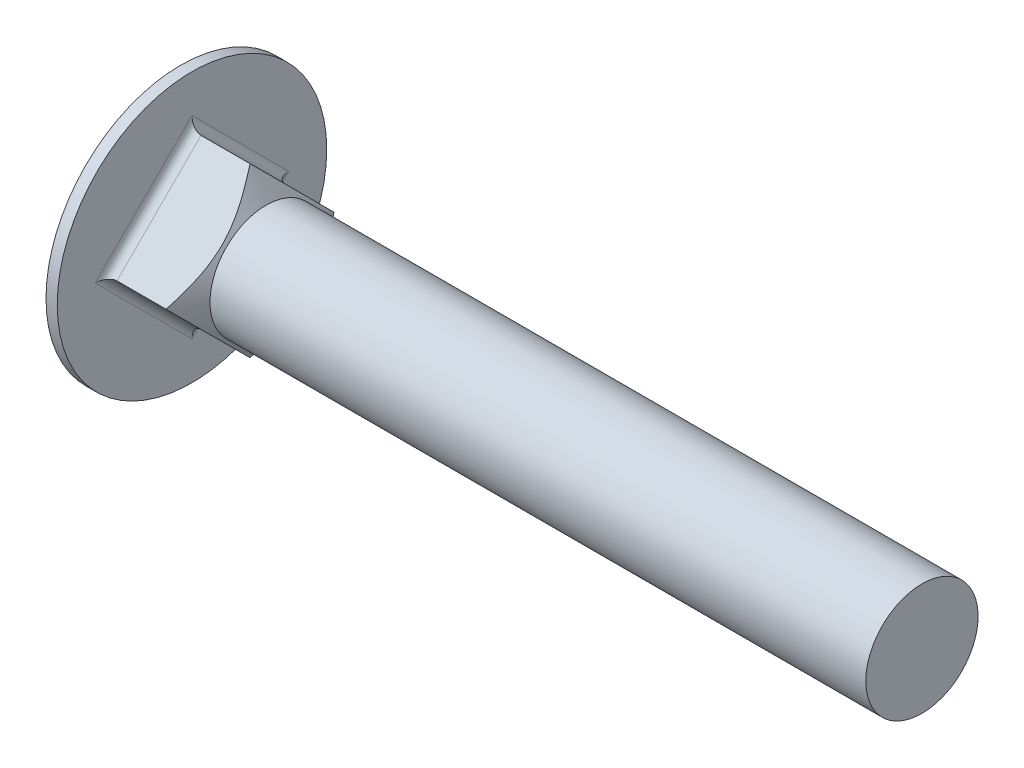
SolidWorks part; units mm, degrees
ref_plane "Front" through (0, 0, 0) normal (0, 0, 1) x (1, 0, 0)
ref_plane "Top" through (0, 0, 0) normal (0, 1, 0) x (1, 0, 0)
ref_plane "Right" through (0, 0, 0) normal (1, 0, 0) x (0, 0, -1)
sketch "Sketch1" plane through (0, 0, 0) normal (0, 0, 1) x (1, 0, 0)
  line L0 (-9.8282, 0) -> (16.3483, 0) construction
  line L1 (4, 12) -> (5, 12)
  line L2 (0, 0) -> (5, 0)
  line L3 (5, 12) -> (5, 0)
  arc A0 (4, 12) -> (0, 0) centre (20, 0) ccw
  dimension "k" = 5
revolve "BaseHead" add sketch "Sketch1" angle 360 about L0
sketch "Sketch2" plane through (5, 0, 0) normal (1, 0, 0) x (0, 0, -1)
  line L1 (-7.4812, 0) -> (0, -7.4812)
  line L2 (0, -7.4812) -> (7.4812, 0)
  line L3 (7.4812, 0) -> (0, 7.4812)
  line L4 (0, 7.4812) -> (-7.4812, 0)
  circle A0 centre (0, 0) radius 5.29 construction
  dimension "Ss" = 10.58
extrude "Neck" add sketch "Sketch2" along normal blind 6.6
sketch "Sketch3" plane through (0, 0, 0) normal (0, 0, 1) x (1, 0, 0)
  line L0 (5, 0) -> (14.6279, 0) construction
  line L1 (11.6, 7.4812) -> (10.1675, 7.4812)
  line L3 (10.1675, 7.4812) -> (11.6, 5)
  line L5 (11.6, 5) -> (11.6, 7.4812)
  dimension "D1" = 30
revolve "Cut-Revolve1" cut sketch "Sketch3" angle 360 about L0
fillet "HeadFillet" radius 0.8 4 edges at (5, 3.7406, -3.7406) (5, -3.7406, -3.7406) (5, -3.7406, 3.7406) (5, 3.7406, 3.7406)
sketch "Sketch4" plane through (0, 0, 0) normal (0, 1, 0) x (1, 0, 0)
  line L0 (-12.2854, 0) -> (59.7905, 0) construction
  line L1 (70, 5) -> (44, 5)
  line L3 (44, 5) -> (11.6, 5)
  line L4 (5, -12) -> (5, 12) construction
  line L5 (70, 5) -> (70, 0)
  line L6 (70, 0) -> (11.6, 0)
  line L7 (11.6, 0) -> (11.6, 5)
  line L10 (11.6, -5) -> (11.6, 5) construction
  dimension "l" = 65
revolve "Revolve1" add sketch "Sketch4" angle 360 about L0
cosmetic thread "ThreadCosmetic1" [suppressed] parameters "b"=26, "dn"=8.376
sketch "Sketch5" plane through (0, 0, 0) normal (0, 0, 1) x (1, 0, 0)
  line L0 (69.594, 5.2) -> (70.406, 5.2)
  line L1 (70.406, 5.2) -> (70.406, 5)
  line L2 (70.406, 5) -> (70, 4.2968)
  line L3 (69.594, 5) -> (70, 4.2968)
  line L4 (69.594, 5.2) -> (69.594, 5)
  line L5 (-65.6461, 0) -> (65.6461, 0) construction
  line L6 (69.594, 5) -> (70.406, 5) construction
  line L7 (70, 5) -> (70, 4.2968) construction
  line L8 (70, -5) -> (70, 5) construction
  line L10 (70, 5) -> (11.6, 5) construction
  point P5 (70, 5.2)
revolve "Cut-Revolve10" [suppressed] cut sketch "Sketch5" angle 360 about L5
pattern_linear "LPattern10" [suppressed] count 27 spacing 0.9744 along (-1, 0, 0) of bodies 106
equation "\"D2@Sketch5\" =  ( \"d@Sketch4\" - \"dn@ThreadCosmetic1\" )  / 2"
equation "\"D3@LPattern10\" = \"D2@Sketch5\" * 1.2"
equation "\"D1@LPattern10\" = \"b@Sketch4\" / \"D3@LPattern10\" "
equation "\"H@Sketch1\" = \"k@Sketch1\" / 5"
